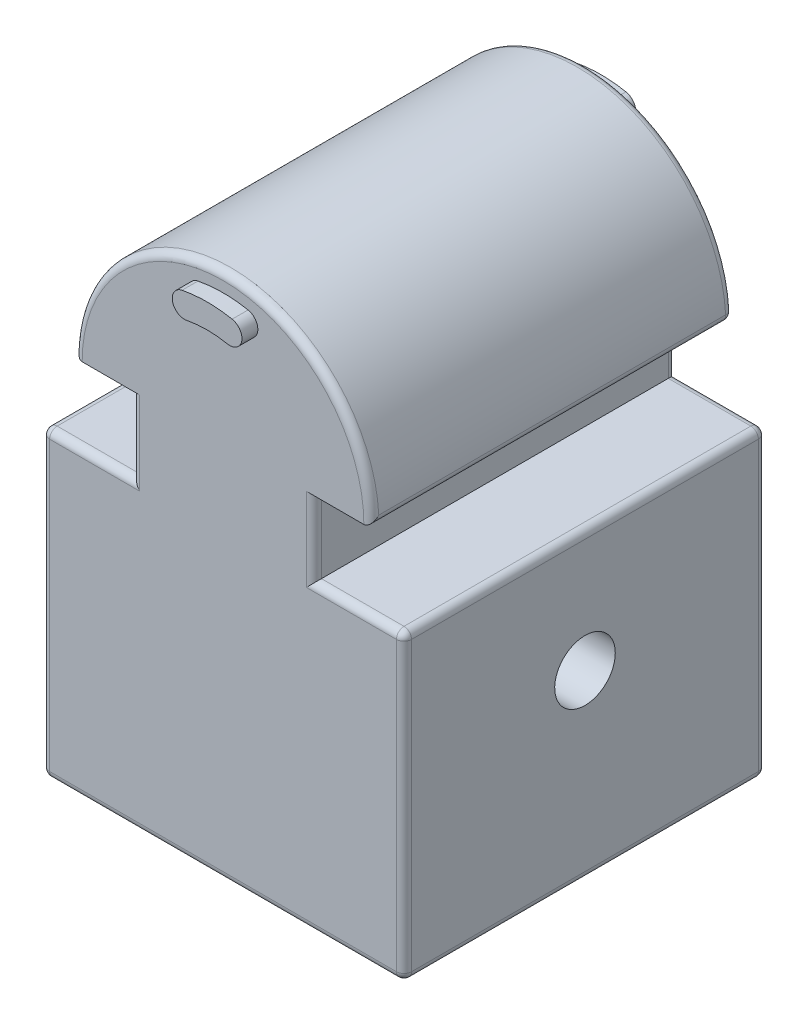
SolidWorks part; units mm, degrees
ref_plane "Front Plane" through (0, 0, 0) normal (0, 0, 1) x (1, 0, 0)
ref_plane "Top Plane" through (0, 0, 0) normal (0, 1, 0) x (1, 0, 0)
ref_plane "Right Plane" through (0, 0, 0) normal (1, 0, 0) x (0, 0, -1)
sketch "Sketch1" plane through (0, 0, 0) normal (0, 0, 1) x (1, 0, 0)
  line L0 (-12.446, 0) -> (12.446, 0)
  line L1 (0, 0) -> (-7.62, 0) construction
  line L2 (0, 9.906) -> (-1.905, 9.906) construction
  line L3 (-7.62, 0) -> (7.62, 0)
  line L7 (0, 9.906) -> (1.905, 9.906) construction
  line L8 (-7.62, -6.35) -> (-15.1765, -6.35)
  line L9 (7.62, -6.35) -> (15.1765, -6.35)
  line L10 (-7.62, -6.35) -> (-7.62, 0)
  line L12 (-15.1765, -6.35) -> (-15.1765, -31.75)
  line L15 (7.62, -6.35) -> (7.62, 0)
  line L16 (-15.1765, -31.75) -> (15.1765, -31.75)
  line L17 (15.1765, -31.75) -> (15.1765, -6.35)
  arc A0 (12.446, 0) -> (-12.446, 0) centre (0, 0) ccw
  arc A1 (8.636, 0) -> (-8.636, 0) centre (0, 0) ccw
  arc A2 (11.176, 0) -> (-11.176, 0) centre (0, 0) ccw
  arc A3 (11.049, 0) -> (-11.049, 0) centre (0, 0) ccw
  arc A4 (8.89, 0) -> (-8.89, 0) centre (0, 0) ccw
  circle A5 centre (0, 0) radius 11.176 construction
  circle A6 centre (0, 0) radius 11.049 construction
  circle A7 centre (0, 0) radius 8.89 construction
  circle A8 centre (0, 0) radius 8.636 construction
  arc A10 (9.906, 0) -> (-9.906, 0) centre (0, 0) ccw construction
  arc A11 (-1.905, 9.7211) -> (1.905, 9.7211) centre (0, 0) cw construction
  arc A12 (2.1004, 10.7181) -> (-2.1004, 10.7181) centre (0, 0) ccw
  arc A13 (1.7096, 8.7241) -> (-1.7096, 8.7241) centre (0, 0) ccw
  arc A14 (1.7096, 8.7241) -> (2.1004, 10.7181) centre (1.905, 9.7211) ccw
  arc A15 (-2.1004, 10.7181) -> (-1.7096, 8.7241) centre (-1.905, 9.7211) ccw
  arc A16 (-1.905, 9.7211) -> (1.905, 9.7211) centre (0, 0) cw construction
  arc A17 (2.1004, 10.7181) -> (-2.1004, 10.7181) centre (0, 0) ccw
  arc A18 (1.7096, 8.7241) -> (-1.7096, 8.7241) centre (0, 0) ccw
  arc A19 (1.7096, 8.7241) -> (2.1004, 10.7181) centre (1.905, 9.7211) ccw
  arc A20 (-2.1004, 10.7181) -> (-1.7096, 8.7241) centre (-1.905, 9.7211) ccw
  point P31 (0, 9.906)
  point P39 (0, 9.906)
  dimension "D1" = 24.892
  dimension "D2" = 22.352
  dimension "D3" = 17.272
  dimension "D8" = 9.906
  dimension "D11" = 8.89
  dimension "D12" = 10.922
  dimension "D4" = 7.62
  dimension "D7" = 0.254
  dimension "D9" = 1.905
  dimension "D10" = 1.905
  dimension "D14" = 7.5565
  dimension "D5" = 7.5565
extrude "Main Body Extrude" add sketch "Sketch1" along normal mid plane 30.353 contours L0 | A12 A15 A4 A14 | L0 A0 region at (0, 9.8081, 0) region at (0, -17.2796, 0)
extrude "Slot Extrude" add sketch "Sketch1<4>" along normal mid plane 33.02 contours A12 A15 A4 A14 region at (0, 9.8081, 0)
sketch "Sketch1<4>" plane through (0, 0, 0) normal (0, 0, 1) x (1, 0, 0) same geometry as "Sketch1"
sketch "Sketch2" plane through (0, -31.75, 0) normal (0, -1, 0) x (1, 0, 0)
  line L1 (-9.525, -9.525) -> (9.525, -9.525)
  line L2 (-9.525, -9.525) -> (-9.525, 9.525)
  line L3 (-9.525, 9.525) -> (9.525, 9.525)
  line L4 (9.525, -9.525) -> (9.525, 9.525)
  line L5 (-9.525, -9.525) -> (9.525, 9.525) construction
  line L6 (-9.525, 9.525) -> (9.525, -9.525) construction
  point P0 (0, 0)
  dimension "D1" = 19.05
  dimension "D2" = 19.05
extrude "Foot Connection Cut" cut sketch "Sketch2" against normal blind 22.86
sketch "Sketch4" plane through (-9.525, 0, 0) normal (1, 0, 0) x (0, 0, -1)
  line L0 (0, -8.89) -> (0, -16.51)
  line L5 (-9.525, -31.75) -> (9.525, -31.75)
  line L6 (9.525, -31.75) -> (9.525, -8.89)
  line L7 (9.525, -8.89) -> (-9.525, -8.89)
  line L8 (-9.525, -8.89) -> (-9.525, -31.75)
  line L9 (-9.525, -31.75) -> (9.525, -31.75)
  line L10 (9.525, -31.75) -> (9.525, -8.89)
  line L11 (9.525, -8.89) -> (-9.525, -8.89)
  line L12 (-9.525, -8.89) -> (-9.525, -31.75)
  circle A0 centre (0, -16.51) radius 2.54
  dimension "D3" = 5.08
  dimension "D1" = 7.62
  dimension "D2" = 0
extrude "Pinhole Cut" cut sketch "Sketch4" against normal mid plane 50.8 contours A0 region at (-9.525, -14.7647, -1.7453)
fillet "Fillet1" radius 0.635 24 edges at (11.3983, -6.35, 15.1765) (12.446, 0, 0) (15.1765, -6.35, 0) (7.62, -3.175, 15.1765) (-11.3982, -6.35, 15.1765) (-15.1765, -6.35, 0) (-7.62, -3.175, 15.1765) (-12.446, 0, 0) (0, 12.446, 15.1765) (11.3983, -6.35, -15.1765) (7.62, -3.175, -15.1765) (10.033, 0, -15.1765) (-10.033, 0, -15.1765) (-7.62, -3.175, -15.1765) (-11.3982, -6.35, -15.1765) (0, 12.446, -15.1765) (15.1765, -31.75, 0) (-15.1765, -31.75, 0) (0, -31.75, 15.1765) (0, -31.75, -15.1765) (-15.1765, -19.05, -15.1765) (-15.1765, -19.05, 15.1765) (15.1765, -19.05, 15.1765) (15.1765, -19.05, -15.1765)
chamfer "Chamfer2" distance 2.54 angle 45 4 edges at (-9.525, -20.32, -9.525) (-9.525, -20.32, 9.525) (9.525, -20.32, -9.525) (9.525, -20.32, 9.525)
chamfer "Chamfer1" distance 2.54 angle 45 8 edges at (9.525, -31.75, 0) (0, -31.75, -9.525) (0, -31.75, 9.525) (-9.525, -31.75, 0) (-8.255, -31.75, 8.255) (8.255, -31.75, 8.255) (8.255, -31.75, -8.255) (-8.255, -31.75, -8.255)
equation "\"InnerBaseDiameter\"=0.98"
equation "\"InnerBaseOuterGroove\"= \"InnerBaseDiameter\" - 0.1"
equation "\"InnerHingeInnerCurve\"= 1"
equation "\"InnerHingeOuterCurve\"= \"InnerHingeInnerCurve\" + 0.1"
equation "\"InnerBaseInnerGroove\"= \"InnerBaseOuterGroove\" - 0.2"
equation "\"InnerHingeWidth\"= 1.45"
equation "\"OuterBaseInnerGroove\"= \"OuterBaseOuterGroove\" - 0.25"
equation "\"OuterBaseDiameter\"= ( ( \"InnerHingeOuterCurve\" / 2 ) ^ 2 + ( \"InnerHingeLength\" / 2 ) ^ 2 ) ^ 0.5 * 2"
equation "\"InnerHingeLength\"=1.2"
equation "\"OuterBaseOuterGroove\"= \"OuterBaseDiameter\" - 0.2"
equation "\"D1@Sketch1\"=\"InnerBaseDiameter\""
equation "\"D2@Sketch1\"=\"InnerBaseOuterGroove\""
equation "\"D3@Sketch1\"=\"InnerBaseInnerGroove\""
equation "\"D8@Sketch1\"=\"InnerBaseOuterGroove\"  * 0.25 +\"InnerBaseInnerGroove\" * 0.25"
equation "\"D11@Sketch1\"=\"InnerBaseInnerGroove\" *0.5 +0.01"
equation "\"D12@Sketch1\"=\"InnerBaseOuterGroove\"*0.5 -0.01"
